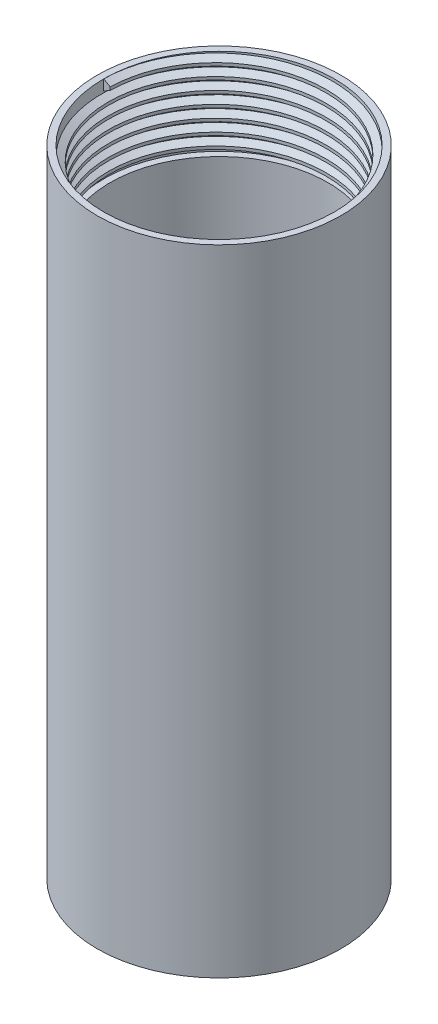
SolidWorks part; units mm, degrees
ref_plane "Front Plane" through (0, 0, 0) normal (0, 0, 1) x (1, 0, 0)
ref_plane "Top Plane" through (0, 0, 0) normal (0, 1, 0) x (1, 0, 0)
ref_plane "Right Plane" through (0, 0, 0) normal (1, 0, 0) x (0, 0, -1)
sketch "Sketch1" plane through (0, 0, 0) normal (0, 1, 0) x (1, 0, 0)
  circle A0 centre (0, 0) radius 14.2875
extrude "Boss-Extrude1" add sketch "Sketch1" along normal blind 74.4601
sketch "Sketch2" plane through (0, 74.4601, 0) normal (0, 1, 0) x (1, 0, 0)
  circle A0 centre (0, 0) radius 12.7762
extrude "Cut-Extrude1" cut sketch "Sketch2" against normal through all
sketch "Sketch5" plane through (0, 74.4601, 0) normal (0, 1, 0) x (1, 0, 0)
  circle A0 centre (0, 0) radius 13.5255
extrude "Cut-Extrude2" cut sketch "Sketch5" against normal blind 10.16
sketch "Sketch6" plane through (0, 0, 0) normal (0, -1, 0) x (1, 0, 0)
  circle A0 centre (0, 0) radius 13.5255
extrude "Cut-Extrude3" cut sketch "Sketch6" against normal blind 10.16
thread "Thread1" pitch 1.4111 method extrude profile "Thread Profile2" start angle 0, offset 0, length 8.89, pitch 1.4111, diameter 27.051
ref_plane "Plane2" through (-13.5255, 74.4601, 0) normal (0, 0, 1) x (-1, 0, 0)
sketch "Thread Profile2" plane through (-13.5255, 74.4601, 0) normal (0, 0, 1) x (-1, 0, 0)
  line L0 (0, 0) -> (0, 1.4111) construction
  line L11 (0, 0) -> (0, 1.2347)
  line L12 (0, 1.2347) -> (-0.7638, 0.7937)
  line L13 (-0.7638, 0.7937) -> (-0.7638, 0.441)
  line L15 (-0.7638, 0.441) -> (0, 0)
  line L17 (-0.7638, 0.6174) -> (0, 0.6174) construction
  point P2 (0, 0)
  dimension "Pitch" = 1.4111
  dimension "Profile_Angle" = 60
  dimension "Profile_Land" = 0.3528
  dimension "Profile_Height" = 0.7638
thread "Thread2" pitch 1.4111 method extrude profile "Thread Profile3" start angle 0, offset 0, length 8.89, pitch 1.4111, diameter 27.051
ref_plane "Plane3" through (13.5255, 0, 0) normal (0, 0, 1) x (1, 0, 0)
sketch "Thread Profile3" plane through (13.5255, 0, 0) normal (0, 0, 1) x (1, 0, 0)
  line L0 (0, 0) -> (0, 1.4111) construction
  line L11 (0, 0) -> (0, 1.2347)
  line L12 (0, 1.2347) -> (-0.7638, 0.7937)
  line L13 (-0.7638, 0.7937) -> (-0.7638, 0.441)
  line L15 (-0.7638, 0.441) -> (0, 0)
  line L17 (-0.7638, 0.6174) -> (0, 0.6174) construction
  point P2 (0, 0)
  dimension "Pitch" = 1.4111
  dimension "Profile_Angle" = 60
  dimension "Profile_Land" = 0.3528
  dimension "Profile_Height" = 0.7638
